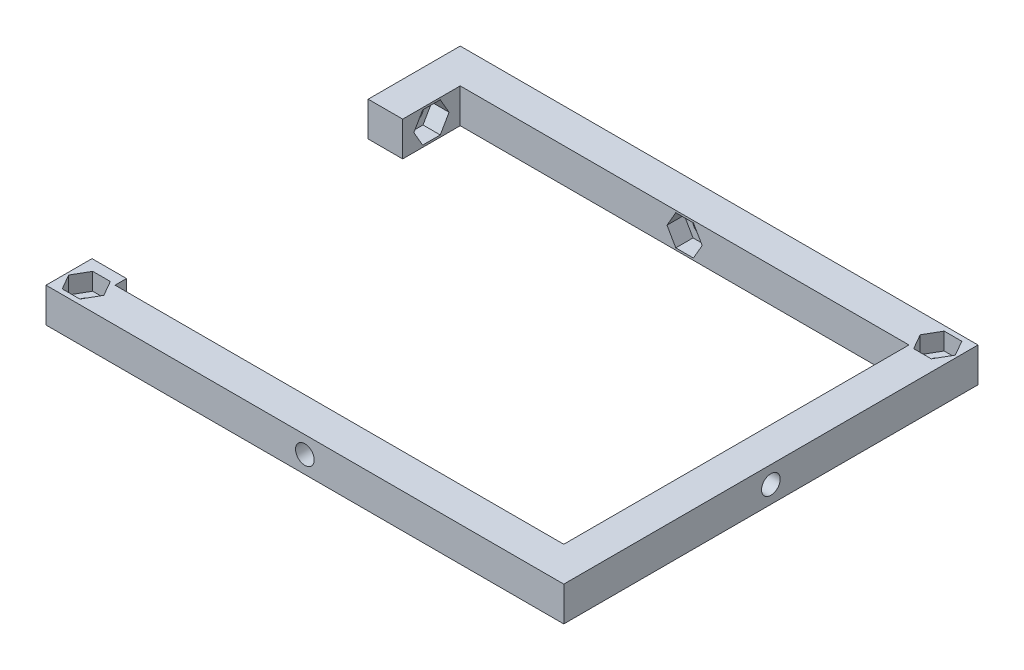
SolidWorks part; units mm, degrees
other "Marca1"
sketch "Croquis7" plane through (-45, 6, 36) normal (-0.6148, 0.4466, 0.6501) x (0.7881, 0.3153, 0.5287)
ref_plane "Alzado" through (0, 0, 0) normal (0, 0, 1) x (1, 0, 0)
ref_plane "Planta" through (0, 0, 0) normal (0, 1, 0) x (1, 0, 0)
ref_plane "Vista lateral" through (0, 0, 0) normal (1, 0, 0) x (0, 0, -1)
sketch "Croquis1" plane through (0, 0, 0) normal (0, 1, 0) x (1, 0, 0)
  line L1 (-45, -36) -> (45, -36)
  line L2 (-45, -36) -> (-45, 36)
  line L3 (-45, 36) -> (45, 36)
  line L4 (45, -36) -> (45, 36)
  line L5 (-45, -36) -> (45, 36) construction
  line L6 (-45, 36) -> (45, -36) construction
  point P0 (0, 0)
  dimension "D1" = 90
  dimension "D2" = 72
extrude "Saliente-Extruir1" add sketch "Croquis1" along normal blind 6
sketch "Croquis2" plane through (0, 6, 0) normal (0, 1, 0) x (1, 0, 0)
  line L0 (-45, 36) -> (-45, -36) construction
  line L1 (-39, -30) -> (39, -30)
  line L2 (-39, -30) -> (-39, 30)
  line L3 (-39, 30) -> (39, 30)
  line L4 (39, -30) -> (39, 30)
  line L5 (-39, -30) -> (39, 30) construction
  line L6 (-39, 30) -> (39, -30) construction
  line L7 (-45, -36) -> (45, -36) construction
  line L8 (45, 36) -> (-45, 36) construction
  line L10 (45, -36) -> (45, 36) construction
  circle A0 centre (-41.5, -32.5) radius 1.5
  circle A1 centre (41.5, 32.5) radius 1.5
  point P0 (0, 0)
  dimension "D3" = 3
  dimension "D4" = 3.5
  dimension "D5" = 3.5
  dimension "D6" = 3.5
  dimension "D7" = 3.5
  dimension "D8" = 3
  dimension "D1" = 78
  dimension "D2" = 60
extrude "Cortar-Extruir1" cut sketch "Croquis2" against normal through all
sketch "Croquis3" plane through (0, 6, 0) normal (0, 1, 0) x (1, 0, 0)
  line L0 (-45, -36) -> (45, -36) construction
  line L1 (-39.97, -29.85) -> (-43.03, -29.85)
  line L2 (-43.03, -29.85) -> (-44.56, -32.5)
  line L3 (-44.56, -32.5) -> (-43.03, -35.15)
  line L4 (-43.03, -35.15) -> (-39.97, -35.15)
  line L5 (-39.97, -35.15) -> (-38.44, -32.5)
  line L6 (-38.44, -32.5) -> (-39.97, -29.85)
  line L7 (-45, 36) -> (-45, -36) construction
  line L8 (45, -36) -> (45, 36) construction
  line L9 (43.03, 35.15) -> (39.97, 35.15)
  line L10 (39.97, 35.15) -> (38.44, 32.5)
  line L11 (38.44, 32.5) -> (39.97, 29.85)
  line L12 (39.97, 29.85) -> (43.03, 29.85)
  line L13 (43.03, 29.85) -> (44.56, 32.5)
  line L14 (44.56, 32.5) -> (43.03, 35.15)
  line L15 (45, 36) -> (-45, 36) construction
  circle A0 centre (-41.5, -32.5) radius 2.65 construction
  circle A1 centre (41.5, 32.5) radius 2.65 construction
  dimension "D1" = 5.3
  dimension "D2" = 3.5
  dimension "D3" = 3.5
  dimension "D4" = 5.3
  dimension "D5" = 3.5
  dimension "D6" = 3.5
extrude "Cortar-Extruir2" cut sketch "Croquis3" against normal blind 3
sketch "Croquis4" plane through (0, 0, 36) normal (0, 0, 1) x (1, 0, 0)
  line L0 (-45, 3) -> (45, 3) construction
  line L1 (-45, 6) -> (-45, 0) construction
  line L2 (45, 6) -> (45, 0) construction
  line L3 (-45, 0) -> (45, 0) construction
  line L4 (0, 6) -> (0, 0) construction
  line L5 (-45, 6) -> (45, 6) construction
  circle A0 centre (0, 3) radius 1.625
  point P15 (0, 3)
  dimension "D1" = 3.25
extrude "Cortar-Extruir3" cut sketch "Croquis4" against normal through all
sketch "Croquis5" plane through (45, 0, 0) normal (1, 0, 0) x (0, 0, -1)
  line L0 (-36, 3) -> (36, 3) construction
  line L1 (-36, 6) -> (-36, 0) construction
  line L2 (36, 6) -> (36, 0) construction
  line L3 (0, 6) -> (0, 0) construction
  line L4 (-36, 6) -> (36, 6) construction
  circle A0 centre (0, 3) radius 1.625
  dimension "D1" = 3.25
extrude "Cortar-Extruir4" cut sketch "Croquis5" against normal up to next
sketch "Croquis6" plane through (0, 0, 36) normal (0, 0, 1) x (1, 0, 0)
  line L0 (-45, 3) -> (45, 3) construction
  line L1 (1.53, 5.65) -> (-1.53, 5.65)
  line L2 (-1.53, 5.65) -> (-3.06, 3)
  line L3 (-3.06, 3) -> (-1.53, 0.35)
  line L4 (-45, 0) -> (45, 0)
  line L5 (45, 0) -> (45, 6)
  line L6 (45, 6) -> (-45, 6)
  line L7 (-45, 6) -> (-45, 0)
  line L8 (-45, 0) -> (45, 0)
  line L9 (45, 0) -> (45, 6)
  line L10 (45, 6) -> (-45, 6)
  line L11 (-45, 6) -> (-45, 0)
  line L12 (-1.53, 0.35) -> (1.53, 0.35)
  line L13 (1.53, 0.35) -> (3.06, 3)
  line L14 (3.06, 3) -> (1.53, 5.65)
  circle A0 centre (0, 3) radius 2.65 construction
  point P2 (0, 3)
  dimension "D2" = 5.3
  dimension "D1" = 0
extrude "Cortar-Extruir5" cut sketch "Croquis6" along normal blind 3 from surface flip side to cut starting at face at (1.625, 3, 30)
sketch "Croquis8" plane through (-45, 0, 0) normal (-1, 0, 0) x (0, 0, 1)
  line L1 (-23.47, 5.65) -> (-26.53, 5.65)
  line L2 (-26.53, 5.65) -> (-28.06, 3)
  line L3 (-28.06, 3) -> (-26.53, 0.35)
  line L4 (-26.53, 0.35) -> (-23.47, 0.35)
  line L5 (-23.47, 0.35) -> (-21.94, 3)
  line L6 (-21.94, 3) -> (-23.47, 5.65)
  line L14 (-36, 3) -> (36, 3) construction
  line L15 (-36, 6) -> (-36, 0) construction
  line L16 (36, 6) -> (36, 0) construction
  circle A0 centre (-25, 3) radius 2.65 construction
  dimension "D1" = 5.3
  dimension "D2" = 11
extrude "Cortar-Extruir6" cut sketch "Croquis8" along normal blind 3 from surface starting at face at (-39, 3, 0)
extrude "Cortar-Extruir8" cut sketch "Croquis6<2>" against normal blind 3 from surface flip side to cut starting at face at (-1.625, 3, -30)
sketch "Croquis6<2>" plane through (0, 0, 36) normal (0, 0, 1) x (1, 0, 0) same geometry as "Croquis6"
sketch "Croquis9" plane through (39, 0, 0) normal (-1, 0, 0) x (0, 0, 1)
  line L1 (1.53, 5.65) -> (-1.53, 5.65)
  line L2 (-1.53, 5.65) -> (-3.06, 3)
  line L3 (-3.06, 3) -> (-1.53, 0.35)
  line L4 (-1.53, 0.35) -> (1.53, 0.35)
  line L5 (1.53, 0.35) -> (3.06, 3)
  line L6 (3.06, 3) -> (1.53, 5.65)
  circle A0 centre (0, 3) radius 2.65 construction
  circle A1 centre (0, 3) radius 1.625 construction
  point P10 (0, 0)
  dimension "D1" = 5.3
extrude "Cortar-Extruir9" cut sketch "Croquis9" against normal blind 3
sketch "Croquis10" plane through (-39, 0, 0) normal (1, 0, 0) x (0, 0, -1)
  line L0 (36, 6) -> (36, 0) construction
  circle A0 centre (25, 3) radius 1.625
  point P4 (-25, 3)
  point P5 (0, 3)
  dimension "D2" = 3.25
  dimension "D1" = 11
extrude "Cortar-Extruir10" cut sketch "Croquis10" against normal up to next
sketch "Croquis11" plane through (0, 6, 0) normal (0, 1, 0) x (1, 0, 0)
  line L0 (-39, 30) -> (-39, -30) construction
  line L1 (-45, 20) -> (-39, 20)
  line L2 (-45, 20) -> (-45, -28)
  line L3 (-45, -28) -> (-39, -28)
  line L4 (-39, 20) -> (-39, -28)
  line L7 (-45, 36) -> (-45, -36) construction
  line L8 (-45, -36) -> (45, -36) construction
  line L9 (45, 36) -> (-45, 36) construction
  point P9 (-45, -16.3129)
  dimension "D1" = 8
  dimension "D2" = 16
extrude "Cortar-Extruir12" cut sketch "Croquis11" against normal up to next
